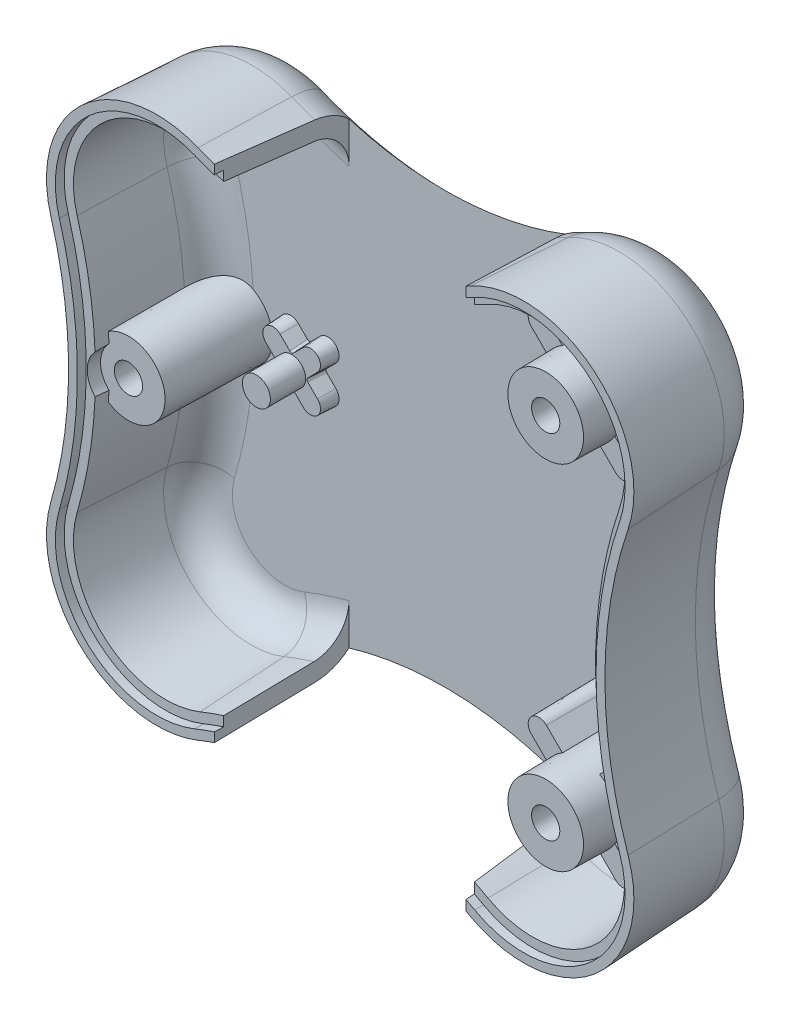
SolidWorks part; units mm, degrees
ref_plane "Front Plane" through (0, 0, 0) normal (0, 0, 1) x (1, 0, 0)
ref_plane "Top Plane" through (0, 0, 0) normal (0, 1, 0) x (1, 0, 0)
ref_plane "Right Plane" through (0, 0, 0) normal (1, 0, 0) x (0, 0, -1)
sketch "Sketch2" plane through (0, 0, 0) normal (0, 0, 1) x (1, 0, 0)
  line L0 (0, 0) -> (0, -39.6111) construction
  line L1 (-20.7952, 17.5) -> (-20.7952, -17.5) construction
  line L2 (0, 0) -> (35.6511, 0) construction
  line L3 (30.0088, 0) -> (30.0088, -21.7321) construction
  arc A0 (32.6379, -16) -> (14.7583, -30.9456) centre (20.7952, -20) cw
  arc A1 (32.6379, 16) -> (14.7583, 30.9456) centre (20.7952, 20) ccw
  arc A2 (32.6379, 16) -> (32.6379, -16) centre (80.0088, 0) ccw
  arc A3 (-16.1129, 29.0899) -> (14.7583, 30.9456) centre (-2.6279, 62.4689) ccw
  arc A4 (-16.1129, -29.0899) -> (14.7583, -30.9456) centre (-2.6279, -62.4689) cw
  arc A5 (-32.7952, -14) -> (-16.1129, -29.0899) centre (-20.7952, -17.5) ccw
  arc A6 (-32.7952, 14) -> (-16.1129, 29.0899) centre (-20.7952, 17.5) cw
  arc A7 (-32.7952, 14) -> (-32.7952, -14) centre (-80.7952, 0) cw
  dimension "D1" = 25
  dimension "D2" = 50
  dimension "D3" = 36
  dimension "D4" = 20.7952
  dimension "D5" = 40
  dimension "D6" = 35
  dimension "D7" = 20.7952
extrude "Boss-Extrude1" add sketch "Sketch2" against normal blind 16.5 draft 3
fillet "Fillet1" radius 6 8 edges at (28.2574, 28.9272, -16.5) (29.1441, 0, -16.5) (28.2574, -28.9272, -16.5) (-0.416, -25.6706, -16.5) (-28.6004, -26.1289, -16.5) (-29.9305, 0, -16.5) (-28.6004, 26.1289, -16.5) (-0.416, 25.6706, -16.5)
shell "Shell1" thickness 2
sketch "Sketch3" plane through (0, 0, 0) normal (0, 1, 0) x (1, 0, 0)
  line L0 (-18.5696, 14.5) -> (17.9258, 14.5) construction
  line L1 (13.5, -14.5) -> (-13.5, -14.5)
  line L2 (13.5, -14.5) -> (13.5, 14.5)
  line L3 (13.5, 14.5) -> (-13.5, 14.5)
  line L4 (-13.5, -14.5) -> (-13.5, 14.5)
  line L5 (13.5, -14.5) -> (-13.5, 14.5) construction
  line L6 (13.5, 14.5) -> (-13.5, -14.5) construction
  point P0 (0, 0)
  dimension "D1" = 27
extrude "Cut-Extrude1" cut sketch "Sketch3" against normal mid plane 110.5
sketch "Sketch4" plane through (0, 0, -14.5) normal (0, 0, 1) x (1, 0, 0)
  circle A0 centre (20.7952, 20) radius 4.5
  circle A1 centre (20.7952, -20) radius 4.5
  dimension "D1" = 9
extrude "Boss-Extrude2" add sketch "Sketch4" along normal blind 12 draft 1
sketch "Sketch16" plane through (0, 0, -2.5) normal (0, 0, 1) x (1, 0, 0)
  circle A0 centre (-26.5, 0) radius 4.15
  dimension "D2" = 8.3
  dimension "D1" = 26.5
extrude "Boss-Extrude9" add sketch "Sketch16" against normal up to body draft 1 draft outward yes
sketch "Sketch6" plane through (0, 0, -14.5) normal (0, 0, 1) x (1, 0, 0)
  line L0 (20.7952, -20) -> (8.416, -20) construction
  line L1 (20.7952, -20) -> (16.0222, -24.773) construction
  line L2 (21.7498, -20.9546) -> (16.9768, -25.7276)
  line L3 (19.8406, -19.0454) -> (15.0676, -23.8184)
  arc A0 (21.7498, -20.9546) -> (19.8406, -19.0454) centre (20.7952, -20) ccw
  arc A1 (15.0676, -23.8184) -> (16.9768, -25.7276) centre (16.0222, -24.773) ccw
  circle A2 centre (20.7952, -20) radius 4.5 construction
  point P3 (18.4087, -22.3865)
  dimension "D1" = 45
  dimension "D2" = 6.75
  dimension "D3" = 2.7
extrude "Boss-Extrude3" add sketch "Sketch6" along normal blind 8 draft 1
pattern_circular "CirPattern1" count 4 over 360 about axis through (20.7952, -20, 0) along (0, 0, 1) of "Boss-Extrude3"
mirror "Mirror1" about plane through (0, 0, 0) normal (0, 1, 0) of "CirPattern1", "Boss-Extrude3"
sketch "Sketch17" plane through (0, 0, -16.5) normal (0, 0, -1) x (-1, 0, 0)
  circle A0 centre (-20.7952, 20) radius 3.75
  circle A1 centre (-20.7952, -20) radius 3.75
  circle A2 centre (26.5, 0) radius 3.75
  dimension "D1" = 7.5
extrude "Cut-Extrude7" cut sketch "Sketch17" against normal blind 11 draft 3
sketch "Sketch18" plane through (0, 0, -5.5) normal (0, 0, -1) x (-1, 0, 0)
  circle A0 centre (-20.7952, 20) radius 1.6
  circle A1 centre (-20.7952, -20) radius 1.6
  circle A2 centre (26.5, 0) radius 1.6
  dimension "D1" = 3.2
extrude "Cut-Extrude8" cut sketch "Sketch18" against normal blind 11
sketch "Sketch7" plane through (0, 0, 0) normal (0, 0, 1) x (1, 0, 0)
  line L2 (-13.5, 26.0545) -> (-13.5, 28.1498)
  line L3 (-13.5, -28.1498) -> (-13.5, -26.0545)
  line L4 (13.5, -28.0582) -> (13.5, -30.2837)
  line L5 (13.5, 30.2837) -> (13.5, 28.0582)
  arc A0 (-13.2139, 27.0127) -> (-13.7861, 25.0963) centre (-13.5, 26.0545) cw
  arc A1 (-12.6479, -26.8486) -> (-13.1895, -24.9233) centre (-12.9187, -25.886) ccw
  arc A2 (-13.2139, -27.0127) -> (-16.4885, -28.1602) centre (-2.6279, -62.4689) ccw construction
  arc A3 (-13.7861, -25.0963) -> (-17.2377, -26.3058) centre (-2.6279, -62.4689) ccw construction
  arc A4 (-16.4885, 28.1602) -> (-13.2139, 27.0127) centre (-2.6279, 62.4689) ccw
  arc A5 (-16.4885, 28.1602) -> (-31.8326, 14.2808) centre (-20.7952, 17.5) ccw
  arc A6 (-31.8326, -14.2808) -> (-31.8326, 14.2808) centre (-80.7952, 0) ccw
  arc A7 (-31.8326, -14.2808) -> (-16.4885, -28.1602) centre (-20.7952, -17.5) ccw
  arc A8 (-12.6479, -26.8486) -> (-16.4885, -28.1602) centre (-2.6279, -62.4689) ccw
  arc A9 (-17.2377, 26.3058) -> (-13.7861, 25.0963) centre (-2.6279, 62.4689) ccw
  arc A10 (-17.2377, 26.3058) -> (-29.9126, 14.8408) centre (-20.7952, 17.5) ccw
  arc A12 (13.9244, 27.1527) -> (16.2085, 28.3162) centre (-2.6279, 62.4689) ccw
  arc A13 (29.7931, 16.9609) -> (16.2085, 28.3162) centre (20.7952, 20) ccw
  arc A14 (-29.9126, -14.8408) -> (-29.9126, 14.8408) centre (-80.7952, 0) ccw
  arc A15 (-29.9126, -14.8408) -> (-17.2377, -26.3058) centre (-20.7952, -17.5) ccw
  arc A16 (-13.1895, -24.9233) -> (-17.2377, -26.3058) centre (-2.6279, -62.4689) ccw
  arc A17 (-16.1129, 29.0899) -> (-13.5, 28.1498) centre (-2.6279, 62.4689) ccw
  arc A18 (-16.1129, 29.0899) -> (-32.7952, 14) centre (-20.7952, 17.5) ccw
  arc A19 (-32.7952, -14) -> (-32.7952, 14) centre (-80.7952, 0) ccw
  arc A20 (-32.7952, -14) -> (-16.1129, -29.0899) centre (-20.7952, -17.5) ccw
  arc A21 (-13.5, -28.1498) -> (-16.1129, -29.0899) centre (-2.6279, -62.4689) ccw
  arc A22 (29.7931, 16.9609) -> (29.7931, -16.9609) centre (80.0088, 0) ccw
  arc A23 (-13.5, -26.0545) -> (-16.8631, -27.233) centre (-2.6279, -62.4689) ccw
  arc A24 (-30.8726, -14.5608) -> (-16.8631, -27.233) centre (-20.7952, -17.5) ccw
  arc A25 (16.2085, -28.3162) -> (29.7931, -16.9609) centre (20.7952, -20) ccw
  arc A26 (-30.8726, -14.5608) -> (-30.8726, 14.5608) centre (-80.7952, 0) ccw
  arc A27 (-16.8631, 27.233) -> (-30.8726, 14.5608) centre (-20.7952, 17.5) ccw
  arc A28 (-16.8631, 27.233) -> (-13.5, 26.0545) centre (-2.6279, 62.4689) ccw
  arc A29 (16.2085, -28.3162) -> (13.1474, -26.7988) centre (-2.6279, -62.4689) ccw
  arc A30 (13.0756, 28.9636) -> (15.2426, 30.0675) centre (-2.6279, 62.4689) ccw
  arc A31 (31.6879, 16.3209) -> (15.2426, 30.0675) centre (20.7952, 20) ccw
  arc A32 (31.6879, 16.3209) -> (31.6879, -16.3209) centre (80.0088, 0) ccw
  arc A33 (15.2426, -30.0675) -> (31.6879, -16.3209) centre (20.7952, -20) ccw
  arc A34 (15.2426, -30.0675) -> (12.3385, -28.628) centre (-2.6279, -62.4689) ccw
  arc A35 (14.7583, -30.9456) -> (13.5, -30.2837) centre (-2.6279, -62.4689) ccw
  arc A36 (-13.5, -26.0545) -> (-16.8631, -27.233) centre (-2.6279, -62.4689) ccw construction
  arc A37 (-30.8726, -14.5608) -> (-16.8631, -27.233) centre (-20.7952, -17.5) ccw construction
  arc A38 (-30.8726, -14.5608) -> (-30.8726, 14.5608) centre (-80.7952, 0) ccw construction
  arc A39 (-16.8631, 27.233) -> (-30.8726, 14.5608) centre (-20.7952, 17.5) ccw construction
  arc A40 (-16.8631, 27.233) -> (-13.5, 26.0545) centre (-2.6279, 62.4689) ccw construction
  arc A41 (14.7583, -30.9456) -> (32.6379, -16) centre (20.7952, -20) ccw
  arc A42 (32.6379, 16) -> (32.6379, -16) centre (80.0088, 0) ccw
  arc A43 (32.6379, 16) -> (14.7583, 30.9456) centre (20.7952, 20) ccw
  arc A44 (13.5, 30.2837) -> (14.7583, 30.9456) centre (-2.6279, 62.4689) ccw
  arc A45 (13.5, 28.0582) -> (15.7255, 29.1919) centre (-2.6279, 62.4689) ccw
  arc A46 (30.7405, 16.6409) -> (15.7255, 29.1919) centre (20.7952, 20) ccw
  arc A47 (30.7405, 16.6409) -> (30.7405, -16.6409) centre (80.0088, 0) ccw
  arc A48 (15.7255, -29.1919) -> (30.7405, -16.6409) centre (20.7952, -20) ccw
  arc A49 (15.7255, -29.1919) -> (13.5, -28.0582) centre (-2.6279, -62.4689) ccw
  arc A50 (13.1474, -26.7988) -> (12.3385, -28.628) centre (12.743, -27.7134) ccw
  arc A52 (15.2426, -30.0675) -> (13.0756, -28.9636) centre (-2.6279, -62.4689) ccw construction
  arc A53 (16.2085, -28.3162) -> (13.9244, -27.1527) centre (-2.6279, -62.4689) ccw construction
  arc A54 (13.0756, 28.9636) -> (13.9244, 27.1527) centre (13.5, 28.0582) ccw
  arc A55 (13.5, 28.0582) -> (15.7255, 29.1919) centre (-2.6279, 62.4689) ccw construction
  arc A56 (30.7405, 16.6409) -> (15.7255, 29.1919) centre (20.7952, 20) ccw construction
  arc A57 (30.7405, 16.6409) -> (30.7405, -16.6409) centre (80.0088, 0) ccw construction
  arc A58 (15.7255, -29.1919) -> (30.7405, -16.6409) centre (20.7952, -20) ccw construction
  arc A59 (15.7255, -29.1919) -> (13.5, -28.0582) centre (-2.6279, -62.4689) ccw construction
  dimension "D1" = 0
  dimension "D2" = 1
  dimension "D3" = 1
  dimension "D4" = 0
  dimension "D5" = 1
  dimension "D6" = 1
extrude "Cut-Extrude9" cut sketch "Sketch7" against normal blind 1
sketch "Sketch19" plane through (0, 0, -2.5) normal (0, 0, 1) x (1, 0, 0)
  circle A0 centre (-26.5, 0) radius 3.175
  dimension "D1" = 6.35
extrude "Cut-Extrude10" cut sketch "Sketch19" along normal blind 3
sketch "Sketch10" plane through (0, 0, -14.5) normal (0, 0, 1) x (1, 0, 0)
  circle A0 centre (-18, 0) radius 1.5875
  dimension "D1" = 3.175
  dimension "D2" = 18
extrude "Boss-Extrude6" add sketch "Sketch10" along normal blind 6
sketch "Sketch11" plane through (0, 0, -14.5) normal (0, 0, 1) x (1, 0, 0)
  line L1 (-13.5, 34.9363) -> (13.5, 34.9363)
  line L2 (-13.5, 34.9363) -> (-13.5, -45.8857)
  line L3 (-13.5, -45.8857) -> (13.5, -45.8857)
  line L4 (13.5, 34.9363) -> (13.5, -45.8857)
  line L6 (13.5, -27.9658) -> (13.5, -23.0847) construction
  point P4 (0, 34.9363)
extrude "Cut-Extrude5" cut sketch "Sketch11" along normal through all draft 3 draft outward yes
sketch "Sketch12" plane through (0, 0, -14.5) normal (0, 0, 1) x (1, 0, 0)
  line L0 (-18, 0) -> (-15.8787, 2.1213) construction
  line L1 (-18.8839, 0.8839) -> (-16.7626, 3.0052)
  line L2 (-17.1161, -0.8839) -> (-14.9948, 1.2374)
  line L3 (-18, 0) -> (0, 0) construction
  arc A0 (-18.8839, 0.8839) -> (-17.1161, -0.8839) centre (-18, 0) ccw
  arc A1 (-14.9948, 1.2374) -> (-16.7626, 3.0052) centre (-15.8787, 2.1213) ccw
  point P3 (-16.9393, 1.0607)
  dimension "D1" = 45
  dimension "D2" = 3
  dimension "D3" = 2.5
extrude "Boss-Extrude7" add sketch "Sketch12" along normal blind 2 draft 3
pattern_circular "CirPattern2" count 4 over 360 about axis through (-18, 0, 0) along (0, 0, 1) of "Boss-Extrude7"
fillet "Fillet3" radius 0.3 4 edges at (-19.6937, 0, -13.5) (-18, 1.6937, -13.5) (-16.3063, 0, -13.5) (-18, -1.6937, -13.5)
